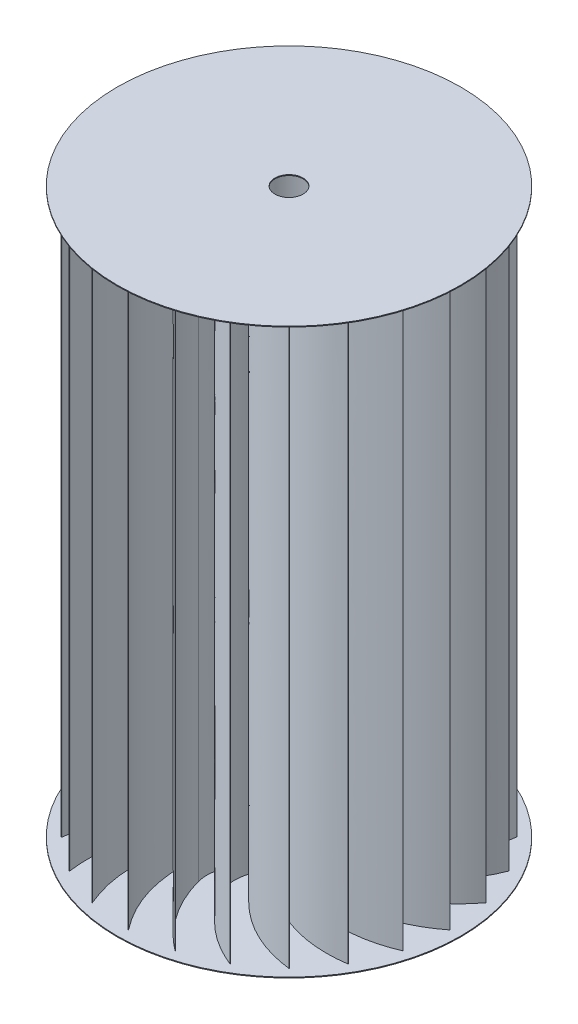
SolidWorks part; units mm, degrees
ref_plane "Front Plane" through (0, 0, 0) normal (0, 0, 1) x (1, 0, 0)
ref_plane "Top Plane" through (0, 0, 0) normal (0, 1, 0) x (1, 0, 0)
ref_plane "Right Plane" through (0, 0, 0) normal (1, 0, 0) x (0, 0, -1)
sketch "Sketch1" plane through (0, 0, 0) normal (0, 1, 0) x (1, 0, 0)
  line L0 (2100.3071, 2494.6898) -> (10579.5647, 2494.6898) construction
  line L1 (0, 0) -> (422.26, 0) construction
  line L2 (422.26, 0) -> (291.39, 0) construction
  line L3 (291.39, 0) -> (291.39, 101.35) construction
  line L4 (357.6003, 101.35) -> (225.1797, 101.35) construction
  line L5 (422.26, -59.8335) -> (422.26, 59.8335) construction
  line L6 (407.7248, 101.35) -> (160.9148, 101.35) construction
  line L7 (0, 0) -> (0.9293, -1.1775)
  line L8 (422.26, 0) -> (420.76, 0)
  line L9 (2.1081, -0.2499) -> (2.1081, -0.2499)
  line L10 (420.5561, 1.4861) -> (420.5561, 1.4861)
  line L11 (0.9293, -1.1775) -> (2.1081, -0.2499)
  line L12 (420.5561, 1.4861) -> (420.76, 0)
  spline S0 degree 3 poles (291.39, 101.35) (387.3282, 101.35) (422.26, 8.8684) (422.26, 0) knots 0 0 0 0 1 1 1 1
  spline S1 degree 3 poles (0, 0) (89.2359, 70.4292) (188.5525, 101.35) (291.39, 101.35) knots 0 0 0 0 1 1 1 1
  spline S2 degree 1 poles (2.1081, -0.2499) (291.39, 99.85) knots 0 0 1 1 construction
  spline S3 degree 1 poles (291.39, 99.85) (420.5561, 1.4861) knots 0 0 1 1 construction
  spline S4 degree 3 poles (2.1081, -0.2499) (4.8667, 1.9144) (10.4461, 6.2004) (21.6354, 14.4339) (35.7761, 24.1736) (52.9507, 34.9657) (76.1234, 48.1867) (105.5732, 62.5497) (141.6152, 76.4261) (178.2863, 87.0429) (215.5107, 94.4996) (246.9383, 98.1625) (272.271, 99.6113) (285.023, 99.85) (291.39, 99.85) knots 0.004414 0.004414 0.004414 0.004414 0.035526 0.066638 0.128862 0.191086 0.25331 0.377759 0.502207 0.626655 0.751103 0.875552 0.937776 1 1 1 1
  spline S5 degree 3 poles (291.39, 99.85) (292.7908, 99.85) (295.6115, 99.8094) (301.0965, 99.5705) (307.7685, 98.985) (315.4515, 97.8512) (325.283, 95.8019) (336.8059, 92.3013) (349.4477, 86.818) (360.9402, 80.2704) (374.7773, 70.4127) (386.4503, 59.301) (396.0838, 47.8185) (402.3197, 39.2439) (407.5972, 30.9298) (411.9472, 23.1004) (414.8251, 17.1674) (416.6947, 12.8897) (417.8844, 9.9445) (418.8651, 7.2926) (419.641, 4.9611) (420.1176, 3.3235) (420.4033, 2.1917) (420.5061, 1.731) (420.5561, 1.4861) knots 0 0 0 0 0.014891 0.029781 0.059562 0.089343 0.119124 0.178686 0.238248 0.29781 0.357372 0.476496 0.536058 0.59562 0.655182 0.714744 0.774306 0.804088 0.833869 0.86365 0.893431 0.923212 0.938102 0.952993 0.952993 0.952993 0.952993
  dimension "D1" = 422.26
  dimension "D2" = 130.87
  dimension "D3" = 101.35
  dimension "D4" = 1.5
  dimension "D5" = 1.5
  dimension "D6" = 1.5
sketch "Sketch2" plane through (0, 0, 0) normal (0, 1, 0) x (1, 0, 0)
  line L0 (422.26, 0) -> (572.26, 0) construction
  circle A0 centre (572.26, 0) radius 150
  circle A1 centre (572.26, 0) radius 147
  dimension "D2" = 3
  dimension "D1" = 150
extrude "Boss-Extrude1" add sketch "Sketch2" along normal blind 2000
extrude "Boss-Extrude2" add sketch "Sketch1" along normal blind 2000 separate body
sketch "Sketch3" plane through (0, 2000, 0) normal (0, 1, 0) x (1, 0, 0)
  line L0 (420.5561, 1.4861) -> (420.76, 0) construction
  line L1 (424.6966, -8.0145) -> (423.9095, 0)
  line L2 (423.9095, 0) -> (420.76, 0)
  line L3 (421.245, -3.5353) -> (420.2742, 3.5417) construction
  spline S0 degree 2 poles (420.76, 0) (421.3668, -4.4231) (424.6966, -8.0145) knots 0 0 0 1 1 1
extrude "Boss-Extrude3" add sketch "Sketch3" against normal blind 2000
pattern_circular "CirPattern3" count 24 over 360 about axis through (572.26, 2000, 0) along (0, -1, 0) of bodies 104
combine bodies "Combine1" operation type add bodies to combine 105 104 106 107 108 109 110 111 112 113 115 114 116 117 118 119 120 121 122 123 124 125 126 127
sketch "Sketch4" plane through (0, 2000, 0) normal (0, 1, 0) x (1, 0, 0)
  circle A0 centre (572.26, 0) radius 610
  circle A1 centre (572.26, 0) radius 147
  dimension "D1" = 1220
  dimension "D2" = 294
extrude "Boss-Extrude4" add sketch "Sketch4" along normal blind 3
sketch "Sketch5" plane through (0, 0, 0) normal (0, -1, 0) x (1, 0, 0)
  circle A0 centre (572.26, 0) radius 610
  circle A1 centre (572.26, 0) radius 147
  dimension "D1" = 1220
  dimension "D2" = 294
extrude "Boss-Extrude5" add sketch "Sketch5" along normal blind 3
sketch "Sketch6" plane through (0, 2003, 0) normal (0, 1, 0) x (1, 0, 0)
  circle A0 centre (572.26, 0) radius 147
  circle A1 centre (572.26, 0) radius 130
  dimension "D1" = 294
  dimension "D2" = 260
extrude "Boss-Extrude6" add sketch "Sketch6" against normal up to surface (2006 mm away) up to face at (572.26, -3, -610)
sketch "Sketch7" plane through (0, 2003, 0) normal (0, 1, 0) x (1, 0, 0)
  circle A0 centre (572.26, 0) radius 130 construction
  circle A1 centre (572.26, 0) radius 130
  circle A2 centre (572.26, 0) radius 50
  dimension "D1" = 100
extrude "Boss-Extrude7" add sketch "Sketch7" against normal blind 3
sketch "Sketch8" plane through (0, -3, 0) normal (0, -1, 0) x (1, 0, 0)
  circle A0 centre (572.26, 0) radius 130 construction
  circle A1 centre (572.26, 0) radius 130
  circle A2 centre (572.26, 0) radius 50 construction
  circle A3 centre (572.26, 0) radius 50
extrude "Boss-Extrude8" add sketch "Sketch8" against normal blind 3
